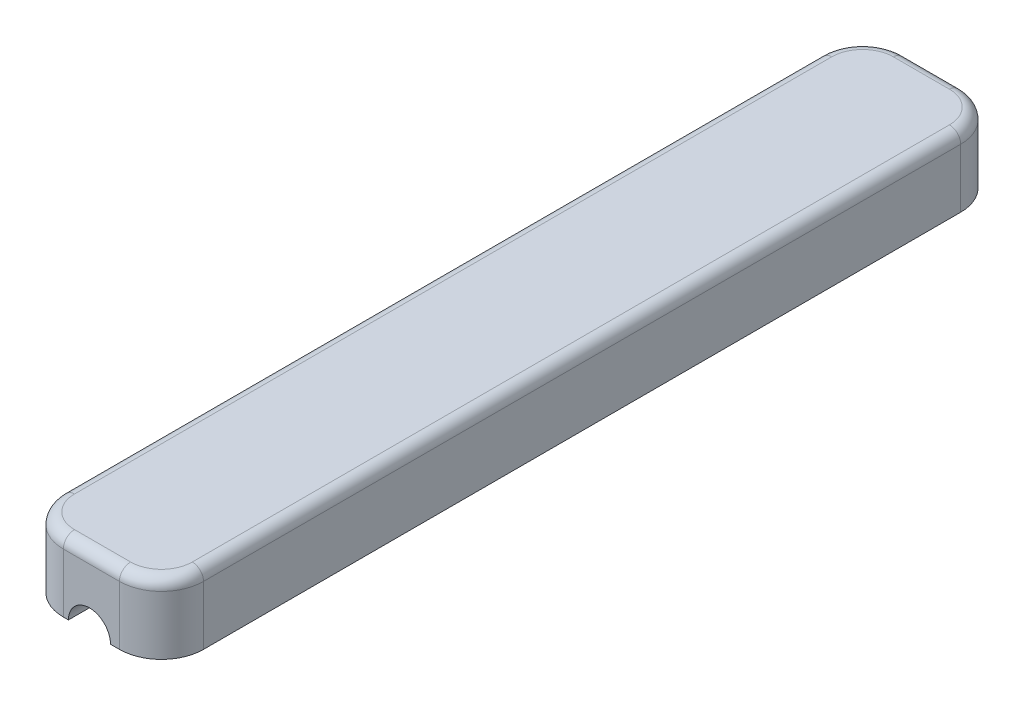
SolidWorks part; units mm, degrees
ref_plane "Plano frontal" through (0, 0, 0) normal (0, 0, 1) x (1, 0, 0)
ref_plane "Plano superior" through (0, 0, 0) normal (0, 1, 0) x (1, 0, 0)
ref_plane "Plano direito" through (0, 0, 0) normal (1, 0, 0) x (0, 0, -1)
sketch "Esboço1" plane through (0, 0, 0) normal (1, 0, 0) x (0, 0, -1)
  line L1 (-150, -12.5) -> (150, -12.5)
  line L2 (-150, -12.5) -> (-150, 12.5)
  line L3 (-150, 12.5) -> (150, 12.5)
  line L4 (150, -12.5) -> (150, 12.5)
  line L5 (-150, -12.5) -> (150, 12.5) construction
  line L6 (-150, 12.5) -> (150, -12.5) construction
  point P0 (0, 0)
  dimension "D1" = 300
  dimension "D2" = 25
extrude "Ressalto-extrusão1" add sketch "Esboço1" along normal blind 50 contours L2 L3 L4 L1
fillet "Filete1" radius 4 4 edges at (25, 12.5, -150) (25, 12.5, 150) (0, 12.5, 0) (50, 12.5, 0)
fillet "Filete2" radius 15 8 edges at (48.8284, 11.3284, 148.8284) (1.1716, 11.3284, 148.8284) (48.8284, 11.3284, -148.8284) (1.1716, 11.3284, -148.8284) (0, -2, -150) (50, -2, -150) (0, -2, 150) (50, -2, 150)
sketch "Esboço8" plane through (0, 0, 0) normal (0, 0, 1) x (1, 0, 0)
  line L0 (35, -12.5) -> (15, -12.5) construction
  circle A0 centre (24.3239, -12.5) radius 7.5
extrude "Corte-extrusão2" cut sketch "Esboço8" against normal through all both and the other way through all
